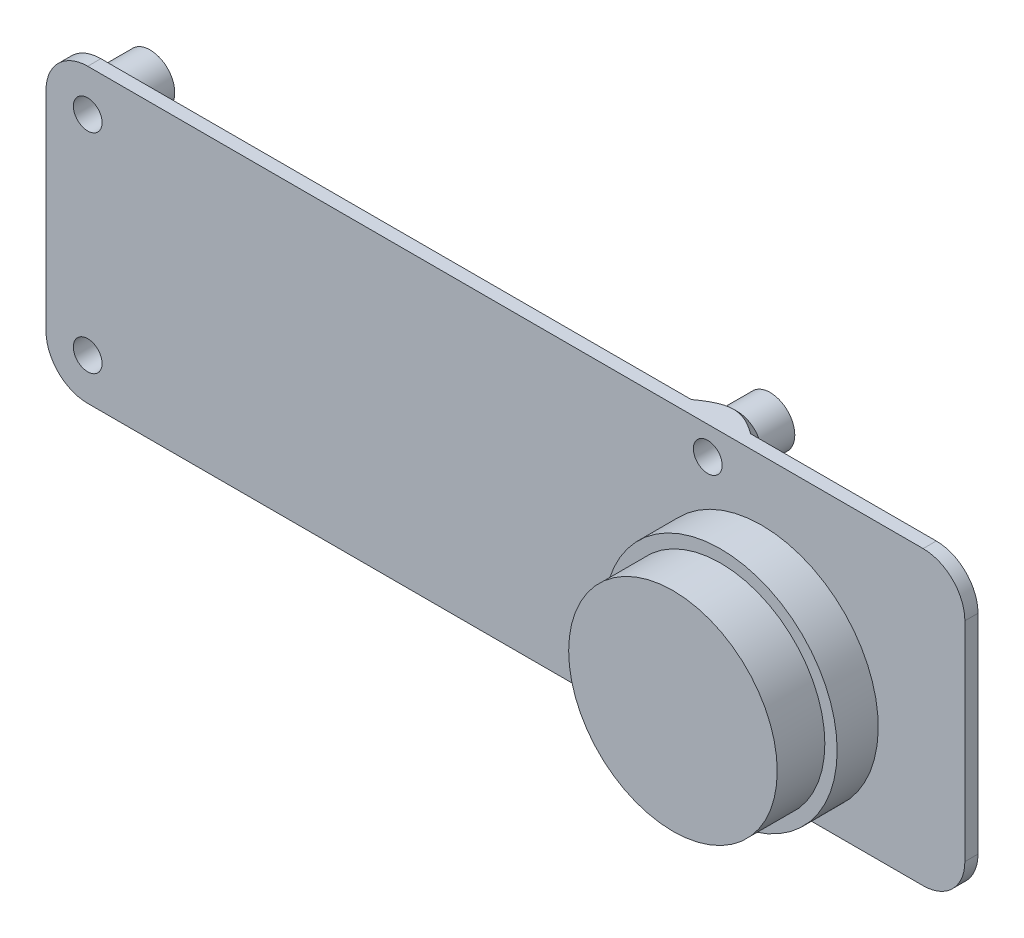
SolidWorks part; units mm, degrees
ref_plane "Front Plane" through (0, 0, 0) normal (0, 0, 1) x (1, 0, 0)
ref_plane "Top Plane" through (0, 0, 0) normal (0, 1, 0) x (1, 0, 0)
ref_plane "Right Plane" through (0, 0, 0) normal (1, 0, 0) x (0, 0, -1)
sketch "Sketch1" plane through (0, 0, 0) normal (0, 0, 1) x (1, 0, 0)
  line L1 (0, 5.08) -> (101.74, 5.08)
  line L2 (-5.08, 0) -> (-5.08, -25.4)
  line L3 (0, -30.48) -> (101.74, -30.48)
  line L4 (106.82, 0) -> (106.82, -25.4)
  circle A0 centre (0, 0) radius 1.75
  circle A1 centre (0, -25.4) radius 1.75
  circle A2 centre (75.51, 1.63) radius 1.75
  circle A3 centre (64.33, -27.48) radius 1.75
  arc A4 (-5.08, -25.4) -> (0, -30.48) centre (0, -25.4) ccw
  arc A5 (101.74, -30.48) -> (106.82, -25.4) centre (101.74, -25.4) ccw
  arc A6 (101.74, 5.08) -> (106.82, 0) centre (101.74, 0) cw
  arc A7 (0, 5.08) -> (-5.08, 0) centre (0, 0) ccw
  point P0 (0, 0)
  point P1 (75.51, 1.63)
  point P3 (64.33, -27.48)
  point P4 (0, -25.4)
  point P19 (-5.08, -30.48)
  point P22 (106.82, -30.48)
  dimension "D6" = 3.5
  dimension "D11" = 5.08
  dimension "D1" = 75.51
  dimension "D2" = 64.33
  dimension "D3" = 1.63
  dimension "D4" = 25.4
  dimension "D5" = 27.48
  dimension "D7" = 35.56
  dimension "D8" = 5.08
  dimension "D9" = 5.08
  dimension "D10" = 111.9
extrude "Boss-Extrude1" add sketch "Sketch1" along normal blind 1.6
sketch "Sketch2" plane through (0, 0, 1.6) normal (0, 0, 1) x (1, 0, 0)
  line L1 (106.82, -25.4) -> (106.82, 0) construction
  line L2 (101.74, 5.08) -> (0, 5.08) construction
  circle A0 centre (82.07, -16.48) radius 12.7
  dimension "D1" = 25.4
  dimension "D3" = 21.56
  dimension "D2" = 24.75
extrude "Boss-Extrude2" add sketch "Sketch2" along normal blind 10.8
sketch "Sketch3" plane through (0, 0, 0) normal (0, 0, -1) x (-1, 0, 0)
  circle A0 centre (0, 0) radius 1.75 construction
  circle A1 centre (0, -25.4) radius 1.75 construction
  circle A2 centre (-64.33, -27.48) radius 1.75 construction
  circle A3 centre (-75.51, 1.63) radius 1.75 construction
  circle A12 centre (0, 0) radius 1.75
  circle A13 centre (0, -25.4) radius 1.75
  circle A14 centre (-64.33, -27.48) radius 1.75
  circle A15 centre (-75.51, 1.63) radius 1.75
  circle A16 centre (-75.51, 1.63) radius 3
  circle A17 centre (-64.33, -27.48) radius 3
  circle A18 centre (0, -25.4) radius 3
  circle A19 centre (0, 0) radius 3
  dimension "D1" = 6
extrude "Boss-Extrude3" add sketch "Sketch3" along normal blind 6
sketch "Sketch4" plane through (0, 0, 1.6) normal (0, 0, 1) x (1, 0, 0)
  circle A0 centre (82.07, -16.48) radius 12.7 construction
  circle A1 centre (82.07, -16.48) radius 12.7
  circle A2 centre (82.07, -16.48) radius 14.2
  dimension "D1" = 1.5
extrude "Boss-Extrude4" add sketch "Sketch4" along normal blind 5
chamfer "Chamfer1" distance 2 angle 45 4 edges at (3, -25.4, 0) (3, 0, 0) (78.51, 1.63, 0) (61.33, -27.48, 0)
